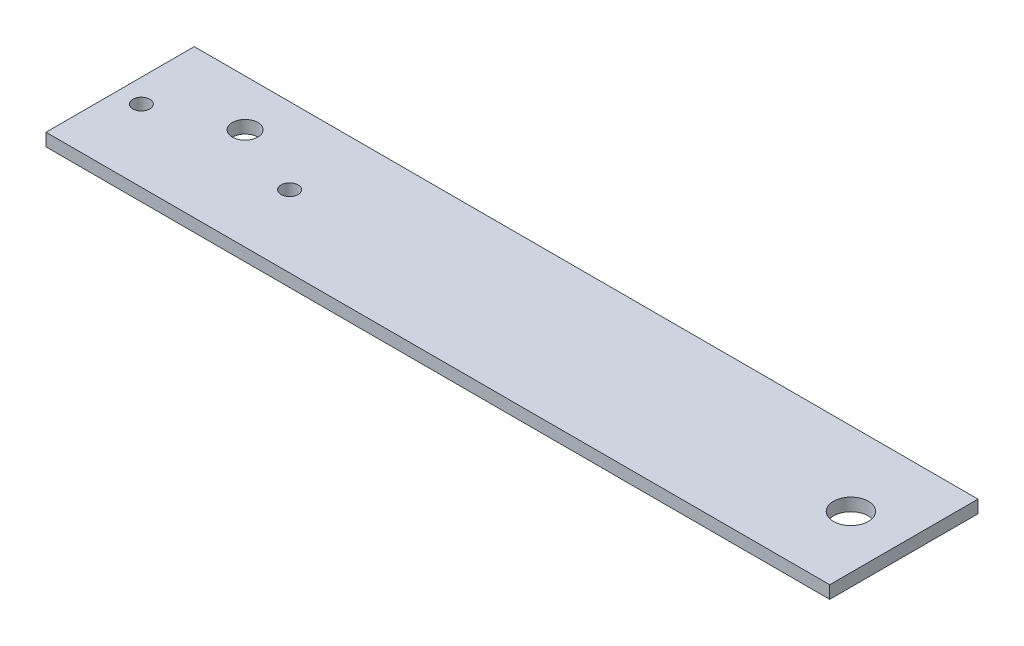
SolidWorks part; units mm, degrees
ref_plane "Front Plane" through (0, 0, 0) normal (0, 0, 1) x (1, 0, 0)
ref_plane "Top Plane" through (0, 0, 0) normal (0, 1, 0) x (1, 0, 0)
ref_plane "Right Plane" through (0, 0, 0) normal (1, 0, 0) x (0, 0, -1)
sketch "Sketch1" plane through (0, 0, 0) normal (0, 1, 0) x (1, 0, 0)
  line L1 (-92.5, 17.5) -> (92.5, 17.5)
  line L2 (-92.5, 17.5) -> (-92.5, -17.5)
  line L3 (-92.5, -17.5) -> (92.5, -17.5)
  line L4 (92.5, 17.5) -> (92.5, -17.5)
  line L5 (-92.5, 17.5) -> (92.5, -17.5) construction
  line L6 (-92.5, -17.5) -> (92.5, 17.5) construction
  circle A0 centre (-10.6801, 3.3392) radius 4.5
  circle A1 centre (-10.6585, -3.6607) radius 14
  circle A2 centre (-28.1585, -4.7634) radius 2
  circle A3 centre (6.8415, -4.7634) radius 2
  circle A4 centre (80, 0) radius 4.125
  point P0 (0, 0)
  point P17 (92.5, 0)
  dimension "D3" = 12.5
  dimension "D4" = 4
  dimension "D5" = 4
  dimension "D6" = 8.25
  dimension "D1" = 35
  dimension "D2" = 185
  dimension "D7" = 8.1025
  dimension "D8" = 8.1025
  dimension "D9" = 17.5
extrude "Boss-Extrude1" add sketch "Sketch1" along normal blind 3 contours A1 L3 L4 L1 L2 A4 A3 A2 | L3 A1 A0 | A2 | A3 | A0 region at (0, 0, -15.6172) region at (-10.656, 0, 4.4565) region at (-28.1585, 0, 4.7634) region at (6.8415, 0, 4.7634)
sketch "Sketch2" plane through (0, 3, 0) normal (0, 1, 0) x (1, 0, 0)
  line L0 (-92.5, 17.5) -> (-92.5, -17.5) construction
  line L1 (-92.5, -17.5) -> (92.5, -17.5) construction
  line L2 (-69.5, 6.5) -> (-69.5, -6.7467) construction
  circle A0 centre (-69.5, 6.5) radius 3
  circle A1 centre (-69.5, 6.5) radius 15 construction
  circle A2 centre (-27, 6.5) radius 27.5 construction
  circle A3 centre (-87, -0.5) radius 2
  circle A4 centre (-52, -0.5) radius 2
  point P14 (0, 0)
  dimension "D1" = 6
  dimension "D3" = 24
  dimension "D4" = 7
  dimension "D2" = 23
  dimension "D5" = 17.5
extrude "Cut-Extrude1" cut sketch "Sketch2" against normal through all
